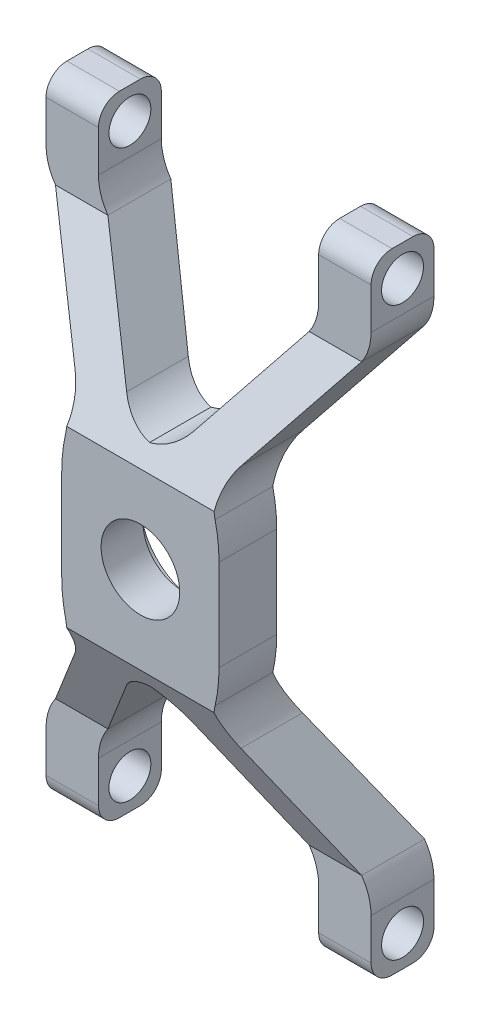
SolidWorks part; units mm, degrees
note: The reader was unsure of these and kept them because the rebuilt part matched: shared geometry of "Sketch5<2>".
material "6061 Alloy"
ref_plane "Front Plane" through (0, 0, 0) normal (0, 0, 1) x (1, 0, 0)
ref_plane "Top Plane" through (0, 0, 0) normal (0, 1, 0) x (1, 0, 0)
ref_plane "Right Plane" through (0, 0, 0) normal (1, 0, 0) x (0, 0, -1)
sketch "Sketch1" plane through (0, 0, 0) normal (0, 0, 1) x (1, 0, 0)
  line L0 (0, 60) -> (0, -60) construction
  line L1 (0, 0) -> (-53.9486, 0) construction
  line L2 (-21, 60) -> (-31, 60)
  line L3 (-31, 60) -> (-31, 48.153)
  line L4 (-29.1915, 42.4172) -> (-11.1273, 16.6188)
  line L5 (-21, 60) -> (-21, 48.153)
  line L6 (-19.1915, 42.4172) -> (-3.3026, 19.7254)
  line L7 (19.1915, 42.4172) -> (3.3026, 19.7254)
  line L8 (21, 60) -> (31, 60)
  line L9 (29.1915, 42.4172) -> (11.1273, 16.6188)
  line L10 (21, 60) -> (21, 48.153)
  line L11 (31, 60) -> (31, 48.153)
  line L12 (-20, 0) -> (20, 0)
  line L13 (-15, 0) -> (-15, 13.2288)
  line L14 (15, 0) -> (15, 13.2288)
  arc A0 (20, 0) -> (-20, 0) centre (0, 0) ccw
  arc A1 (29.1915, 42.4172) -> (31, 48.153) centre (21, 48.153) ccw
  arc A2 (19.1915, 42.4172) -> (21, 48.153) centre (11, 48.153) ccw
  arc A3 (-21, 48.153) -> (-19.1915, 42.4172) centre (-11, 48.153) ccw
  arc A4 (-31, 48.153) -> (-29.1915, 42.4172) centre (-21, 48.153) ccw
  point P20 (31, 45)
  point P23 (21, 45)
  point P26 (-21, 45)
  point P29 (-31, 45)
  dimension "D4" = 40
  dimension "D8" = 10
  dimension "D1" = 120
  dimension "D2" = 42
  dimension "D3" = 10
  dimension "D5" = 215
  dimension "D6" = 15
  dimension "D7" = 15
  dimension "D9" = 5
extrude "Boss-Extrude1" add sketch "Sketch1" along normal blind 30 contours L12 A0 | L3 A4 L4 A0 L6 A3 L5 L2 | A2 L7 A0 L9 A1 L11 L8 L10
sketch "Sketch2" plane through (0, 0, 0) normal (1, 0, 0) x (0, 0, -1)
  line L0 (-25, 0) -> (-25, 16.6188)
  line L1 (-30, 0) -> (0, 0) construction
  line L2 (-30, 16.6188) -> (0, 16.6188) construction
  line L3 (-25, 16.6188) -> (-12, 42.4172)
  line L4 (-30, 42.4172) -> (0, 42.4172) construction
  line L5 (-12, 42.4172) -> (-12, 60)
  line L6 (-30, 60) -> (0, 60) construction
  line L7 (0, 60) -> (0, 48.153) construction
  line L8 (-30, 16.6188) -> (-30, 13.2288) construction
  line L9 (-25, 0) -> (-30, 0)
  line L10 (-30, 0) -> (-30, 60)
  line L11 (-30, 60) -> (-30, 48.153) construction
  line L12 (-30, 60) -> (-12, 60)
  dimension "D2" = 5
  dimension "D1" = 12
extrude "Cut-Extrude1" cut sketch "Sketch2" against normal through all and the other way through all
fillet "Fillet1" radius 10 2 edges at (11.1273, 16.6188, 12.5) (-11.1273, 16.6188, 12.5)
fillet "Fillet2" radius 30 2 edges at (-15, 13.2288, 12.5) (15, 13.2288, 12.5)
sketch "Sketch3" plane through (0, 0, 0) normal (1, 0, 0) x (0, 0, -1)
  line L0 (-14, 0) -> (-14, 15.3603)
  line L1 (-25, 0) -> (0, 0) construction
  line L2 (-25, 15.3603) -> (0, 15.3603) construction
  line L3 (-14, 15.3603) -> (0, 42.4172)
  line L4 (0, 42.4172) -> (0, 0)
  line L5 (0, 0) -> (-14, 0)
  dimension "D1" = 14
extrude "Cut-Extrude2" cut sketch "Sketch3" against normal through all and the other way through all
fillet "Fillet3" radius 10 2 edges at (3.3026, 19.7254, 17.5879) (-3.3026, 19.7254, 17.5879)
ref_point "Point1"
sketch "Sketch4" plane through (31, 0, 0) normal (1, 0, 0) x (0, 0, -1)
  circle A0 centre (-6, 54.0765) radius 4
  dimension "D1" = 8
extrude "Cut-Extrude3" cut sketch "Sketch4" against normal through all
fillet "Fillet4" radius 4 4 edges at (-26, 60, 12) (-26, 60, 0) (26, 60, 12) (26, 60, 0)
mirror "Mirror2" about plane through (0, 0, 30) normal (0, 1, 0) of bodies 106 104
sketch "Sketch5" plane through (0, 0, 14) normal (0, 0, -1) x (-1, 0, 0)
  circle A0 centre (0, 0) radius 11
  circle A1 centre (0, 0) radius 7.5
  dimension "D1" = 22
  dimension "D2" = 15
extrude "Cut-Extrude4" cut sketch "Sketch5" against normal blind 3
extrude "Cut-Extrude6" cut sketch "Sketch5<2>" against normal through all contours A1
sketch "Sketch5<2>" plane through (0, 0, 14) normal (0, 0, -1) x (-1, 0, 0) same geometry as "Sketch5"
